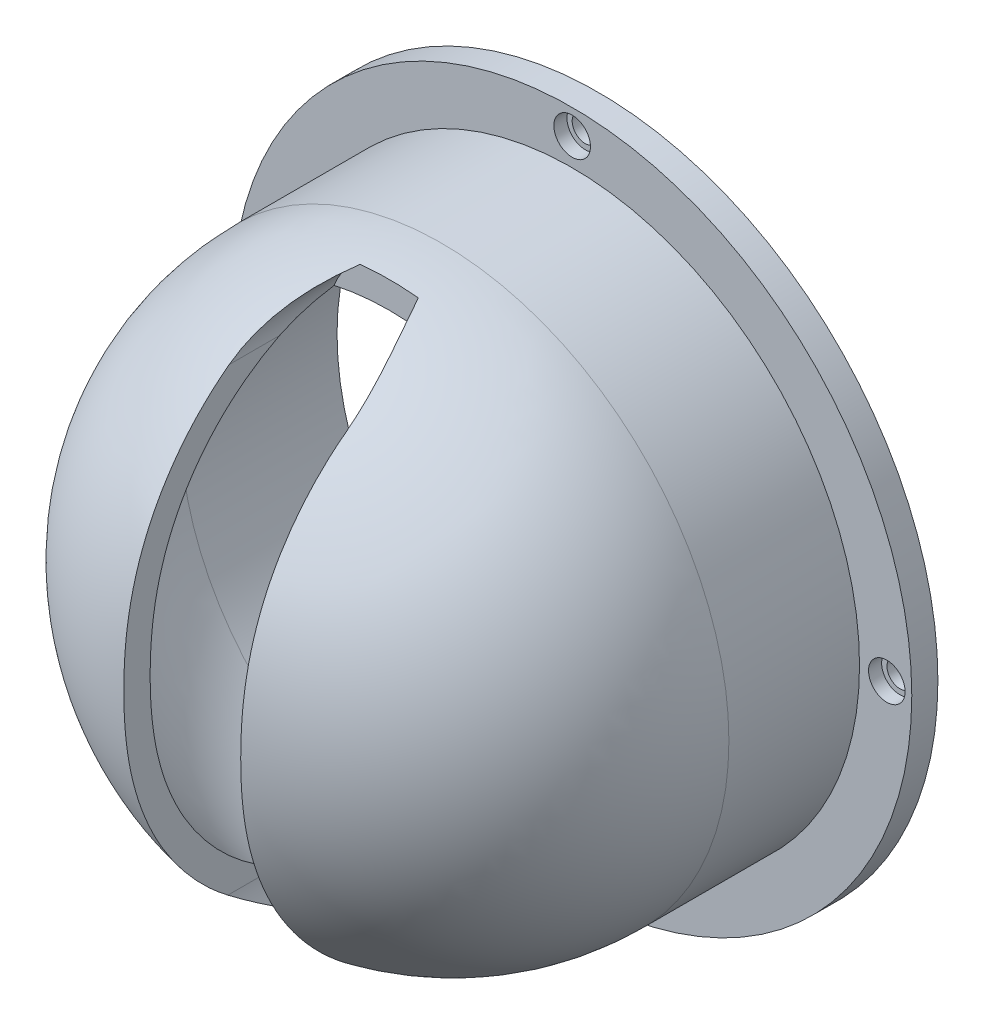
SolidWorks part; units mm, degrees
ref_plane "Front Plane" through (0, 0, 0) normal (1, 0, 0) x (0, 1, 0)
ref_plane "Top Plane" through (0, 0, 0) normal (0, 0, 1) x (0, 1, 0)
ref_plane "Right Plane" through (0, 0, 0) normal (0, 1, 0) x (-1, 0, 0)
sketch "Sketch2" plane through (0, 0, 0) normal (0, 0, 1) x (0, 1, 0)
  circle A0 centre (0, 0) radius 65
  dimension "D1" = 130
extrude "Boss-Extrude1" add sketch "Sketch2" along normal blind 5
sketch "Sketch3" plane through (0, 0, 5) normal (0, 0, 1) x (1, 0, 0)
  circle A0 centre (0, 0) radius 55
  dimension "D1" = 110
extrude "Boss-Extrude2" add sketch "Sketch3" along normal blind 75
fillet "Fillet4" radius 50 1 edges at (55, 0, 80)
shell "Shell1" thickness 5 removed face at (65, 0, 0)
sketch "Sketch7" plane through (0, 0, 5) normal (0, 0, 1) x (1, 0, 0)
  circle A0 centre (0, 60.2478) radius 2.5
  dimension "D1" = 5
extrude "Cut-Extrude2" cut sketch "Sketch7" against normal blind 5
sketch "Sketch8" plane through (0, 0, 5) normal (0, 0, 1) x (1, 0, 0)
  circle A0 centre (0, 60.2236) radius 3.5
  dimension "D1" = 7
extrude "Cut-Extrude3" cut sketch "Sketch8" against normal blind 2.5
pattern_circular "CirPattern1" count 4 over 360 about axis through (0, 0, 5) along (0, 0, -1) of "Cut-Extrude3", "Cut-Extrude2" reverse direction yes
sketch "Sketch11" plane through (0, 0, 80) normal (0, 0, 1) x (1, 0, 0)
  line L0 (0, -43.8118) -> (0, 43.9995) construction
  line L1 (-11.1862, -43.8118) -> (-11.1862, 43.9995)
  line L2 (11.1862, -43.8118) -> (11.1862, 43.9995)
  arc A0 (-11.1862, -43.8118) -> (11.1862, -43.8118) centre (0, -43.8118) ccw
  arc A1 (11.1862, 43.9995) -> (-11.1862, 43.9995) centre (0, 43.9995) ccw
  point P3 (0, 0.0939)
extrude "Cut-Extrude4" cut sketch "Sketch11" against normal blind 40
